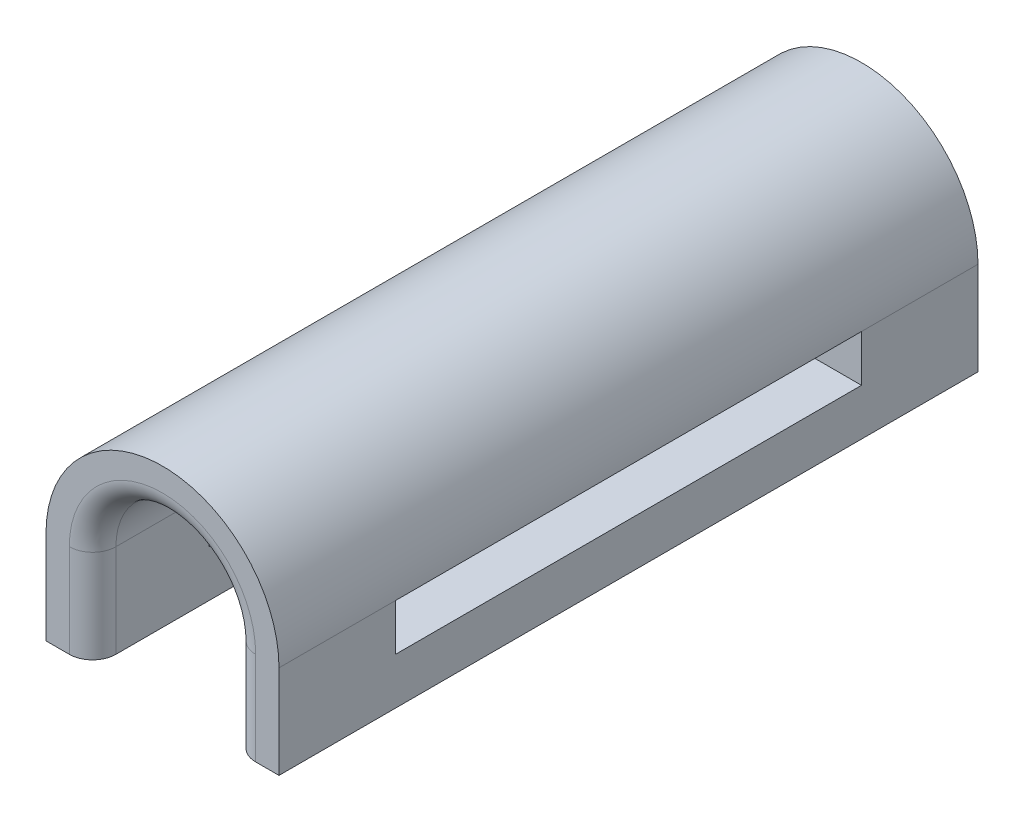
SolidWorks part; units mm, degrees
ref_plane "Płaszczyzna przednia" through (0, 0, 0) normal (0, 0, 1) x (1, 0, 0)
ref_plane "Płaszczyzna górna" through (0, 0, 0) normal (0, 1, 0) x (1, 0, 0)
ref_plane "Płaszczyzna prawa" through (0, 0, 0) normal (1, 0, 0) x (0, 0, -1)
sketch "Szkic1" plane through (0, 0, 0) normal (0, 0, 1) x (1, 0, 0)
  line L0 (-1.5, 0) -> (1.5, 0)
  line L1 (-2.5, 0) -> (-1.5, 0)
  line L2 (1.5, 0) -> (2.5, 0)
  arc A2 (-1.5, 0) -> (1.5, 0) centre (0, 0) cw
  arc A3 (-2.5, 0) -> (2.5, 0) centre (0, 0) cw
  dimension "D1" = 3
  dimension "D2" = 5
extrude "Dodanie-wyciągnięcie2" add sketch "Szkic1" along normal blind 15 contours A3 L1 A2 L2 region at (-2, 0.0559, 0)
sketch "Szkic3" plane through (0, 0, 0) normal (0, -1, 0) x (1, 0, 0)
  line L0 (-1.5, 15) -> (-1.5, 0) construction
  line L1 (-2.5, 15) -> (-1.5, 15)
  line L2 (-2.5, 15) -> (-2.5, 12.5)
  line L3 (-2.5, 12.5) -> (-1.5, 12.5)
  line L4 (-1.5, 15) -> (-1.5, 12.5)
  line L5 (1.5, 15) -> (1.5, 0) construction
  line L6 (2.5, 15) -> (1.5, 15)
  line L7 (2.5, 15) -> (2.5, 12.5)
  line L8 (2.5, 12.5) -> (1.5, 12.5)
  line L9 (1.5, 15) -> (1.5, 12.5)
  line L11 (2.5, 0) -> (1.5, 0)
  line L12 (2.5, 0) -> (2.5, 2.5)
  line L13 (2.5, 2.5) -> (1.5, 2.5)
  line L14 (1.5, 0) -> (1.5, 2.5)
  line L15 (-2.5, 0) -> (-1.5, 0)
  line L16 (-2.5, 0) -> (-2.5, 2.5)
  line L17 (-2.5, 2.5) -> (-1.5, 2.5)
  line L18 (-1.5, 0) -> (-1.5, 2.5)
  dimension "D1" = 10
extrude "Dodanie-wyciągnięcie3" add sketch "Szkic3" along normal blind 2
sketch "Szkic4" plane through (0, 0, 12.5) normal (0, 0, -1) x (-1, 0, 0)
  line L0 (1.5, -2) -> (1.5, 0) construction
  line L1 (2.5, -2) -> (1.5, -2)
  line L2 (2.5, -2) -> (2.5, -1)
  line L3 (2.5, -1) -> (1.5, -1)
  line L4 (1.5, -2) -> (1.5, -1)
  line L5 (-2.5, -2) -> (-2.5, 0) construction
  line L6 (-1.5, -2) -> (-2.5, -2)
  line L7 (-1.5, -2) -> (-1.5, -1)
  line L8 (-1.5, -1) -> (-2.5, -1)
  line L9 (-2.5, -2) -> (-2.5, -1)
  dimension "D1" = 1
extrude "Dodanie-wyciągnięcie4" add sketch "Szkic4" along normal blind 10
fillet "Zaokrąglenie1" radius 0.5 6 edges at (-1.5, -1, 0) (1.5, -1, 0) (-1.5, -1, 15) (1.5, -1, 15) (0, 1.5, 0) (0, 1.5, 15)
